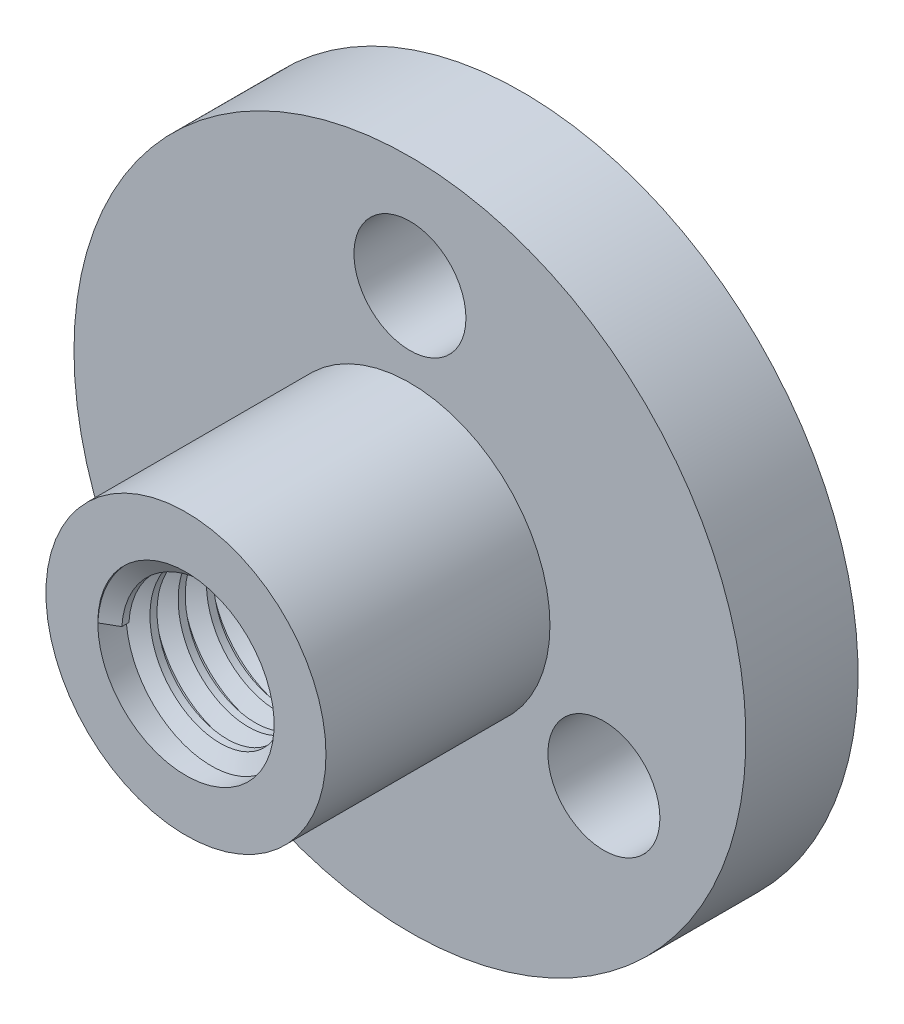
SolidWorks part; units mm, degrees
ref_plane "Front Plane" through (0, 0, 0) normal (0, 0, 1) x (1, 0, 0)
ref_plane "Top Plane" through (0, 0, 0) normal (0, 1, 0) x (1, 0, 0)
ref_plane "Right Plane" through (0, 0, 0) normal (1, 0, 0) x (0, 0, -1)
sketch "Sketch1" plane through (0, 0, 0) normal (0, 0, 1) x (1, 0, 0)
  circle A0 centre (0, 0) radius 9.525
  dimension "D1" = 19.05
extrude "Boss-Extrude1" add sketch "Sketch1" along normal blind 3.18
sketch "Sketch2" plane through (0, 0, 3.18) normal (0, 0, 1) x (1, 0, 0)
  circle A0 centre (0, 0) radius 3.97
  dimension "D1" = 7.94
extrude "Boss-Extrude2" add sketch "Sketch2" along normal blind 6.35
sketch "Sketch3" plane through (0, 0, 9.53) normal (0, 0, 1) x (1, 0, 0)
  circle A0 centre (0, 0) radius 2.5
  dimension "D1" = 5
extrude "Cut-Extrude1" cut sketch "Sketch3" against normal up to surface (9.53 mm away) up to face at (9.525, 0, 0)
sketch "Sketch4" plane through (0, 0, 3.18) normal (0, 0, 1) x (1, 0, 0)
  circle A0 centre (0, 6.35) radius 1.5875
  dimension "D1" = 3.175
  dimension "D2" = 6.35
extrude "Cut-Extrude2" cut sketch "Sketch4" against normal up to surface (3.18 mm away) up to face at (2.5, 0, 0)
pattern_circular "CirPattern1" count 3 over 360 about axis through (0, 0, 9.53) along (0, 0, 1) of "Cut-Extrude2"
thread "Thread1" pitch 0.8 method extrude trim with end face yes profile "Thread Profile1" start angle 0, offset 0, length 0, pitch 0.8, diameter 5
ref_plane "Plane1" through (-2.5, 0, 9.53) normal (0, -1, 0) x (-1, 0, 0)
sketch "Thread Profile1" plane through (-2.5, 0, 9.53) normal (0, -1, 0) x (-1, 0, 0)
  line L0 (0, 0) -> (0, 0.8) construction
  line L11 (0, 0) -> (0, 0.7)
  line L12 (0, 0.7) -> (-0.433, 0.45)
  line L13 (-0.433, 0.45) -> (-0.433, 0.25)
  line L15 (-0.433, 0.25) -> (0, 0)
  line L17 (-0.433, 0.35) -> (0, 0.35) construction
  point P2 (0, 0)
  dimension "Pitch" = 0.8
  dimension "Profile_Angle" = 60
  dimension "Profile_Land" = 0.2
  dimension "Profile_Height" = 0.433
